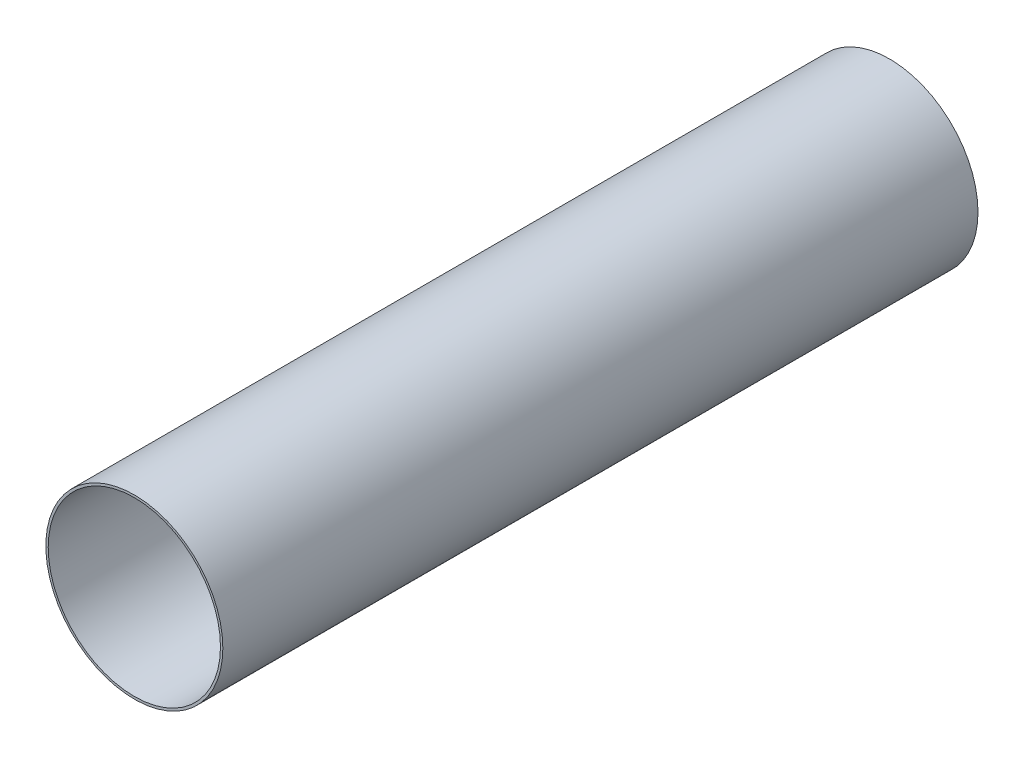
SolidWorks part; units mm, degrees
material "Fibra di Carbonio"
ref_plane "Piano frontale" through (0, 0, 0) normal (0, 0, 1) x (1, 0, 0)
ref_plane "Piano superiore" through (0, 0, 0) normal (0, 1, 0) x (1, 0, 0)
ref_plane "Piano destro" through (0, 0, 0) normal (1, 0, 0) x (0, 0, -1)
sketch "Schizzo1" plane through (0, 0, 0) normal (0, 0, 1) x (1, 0, 0)
  circle A0 centre (0, 0) radius 75
  dimension "D1" = 150
extrude "Estrusione-Sottile1" add sketch "Schizzo1" along normal blind 640 thin thin type one direction reverse wall 2
